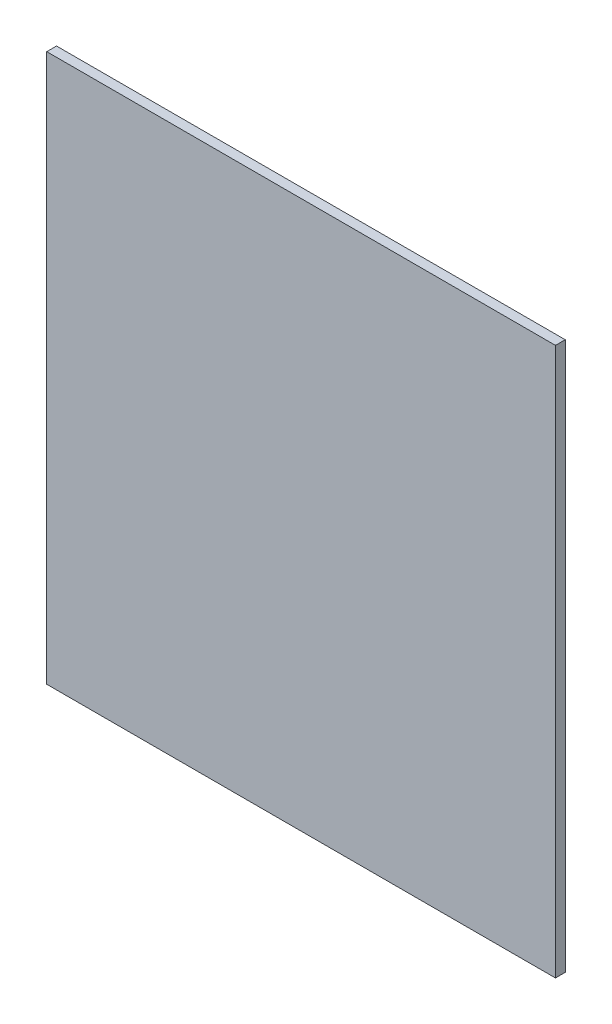
SolidWorks part; units mm, degrees
material "Acrylic (Medium-high impact)"
ref_plane "Front" through (0, 0, 0) normal (0, 0, 1) x (1, 0, 0)
ref_plane "Top" through (0, 0, 0) normal (0, 1, 0) x (1, 0, 0)
ref_plane "Right" through (0, 0, 0) normal (1, 0, 0) x (0, 0, -1)
sketch "Sketch1" plane through (0, 0, 0) normal (0, 0, 1) x (1, 0, 0)
  line L1 (0, 0) -> (165.1, 0)
  line L2 (0, 0) -> (0, 177.8)
  line L3 (0, 177.8) -> (165.1, 177.8)
  line L4 (165.1, 0) -> (165.1, 177.8)
  point P5 (177.9198, 157.9953)
extrude "Boss-Extrude1" add sketch "Sketch1" against normal blind 3.175
